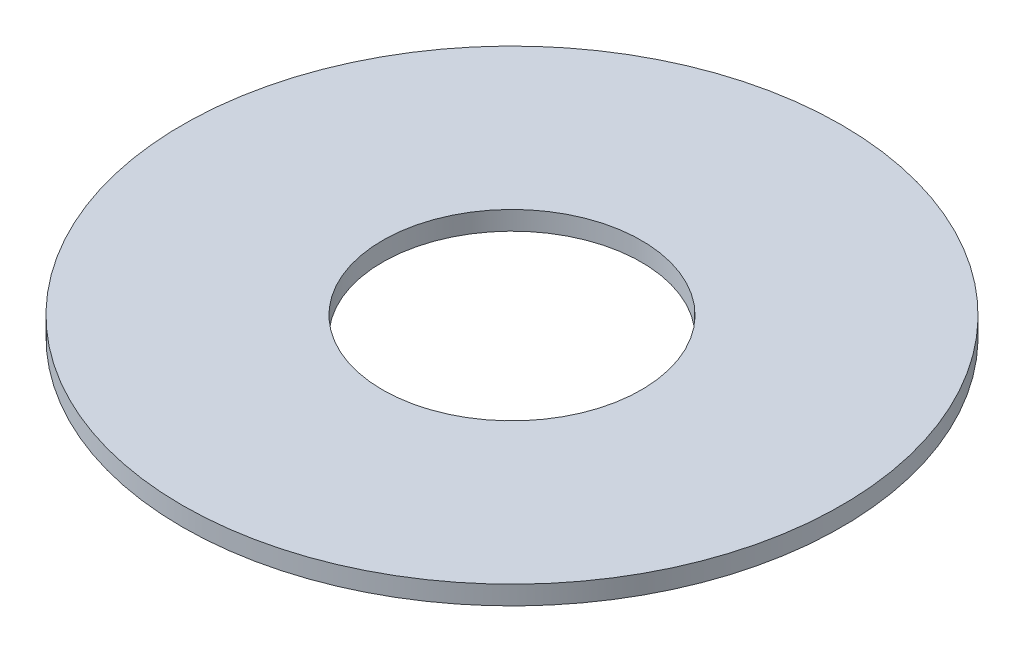
SolidWorks part; units mm, degrees
ref_plane "Front Plane" through (0, 0, 0) normal (0, 0, 1) x (1, 0, 0)
ref_plane "Top Plane" through (0, 0, 0) normal (0, 1, 0) x (1, 0, 0)
ref_plane "Right Plane" through (0, 0, 0) normal (1, 0, 0) x (0, 0, -1)
sketch "Sketch1" plane through (0, 0, 0) normal (0, 1, 0) x (1, 0, 0)
  circle A0 centre (0, 0) radius 70
  dimension "FLANGE_OD" = 140
extrude "Boss-Extrude1" add sketch "Sketch1" along normal blind 4
sketch "Sketch2" plane through (0, 0, 0) normal (0, 1, 0) x (1, 0, 0)
  circle A0 centre (0, 0) radius 27.5
  dimension "BORE_D" = 55
extrude "Cut-Extrude1" cut sketch "Sketch2" along normal through all
sketch "Sketch3" plane through (0, 4, 0) normal (0, 1, 0) x (1, 0, 0)
  circle A0 centre (0, 0) radius 16.9273 construction
  circle A1 centre (-16.9273, 0) radius 1.6122
  dimension "BOLT_D" = 3.2244
  dimension "BOLT_PCD" = 33.8546
extrude "Cut-Extrude2" cut sketch "Sketch3" against normal blind 3.0407 rebuild error yes
pattern_circular "CirPattern1" count 5 over 360 rebuild error yes
